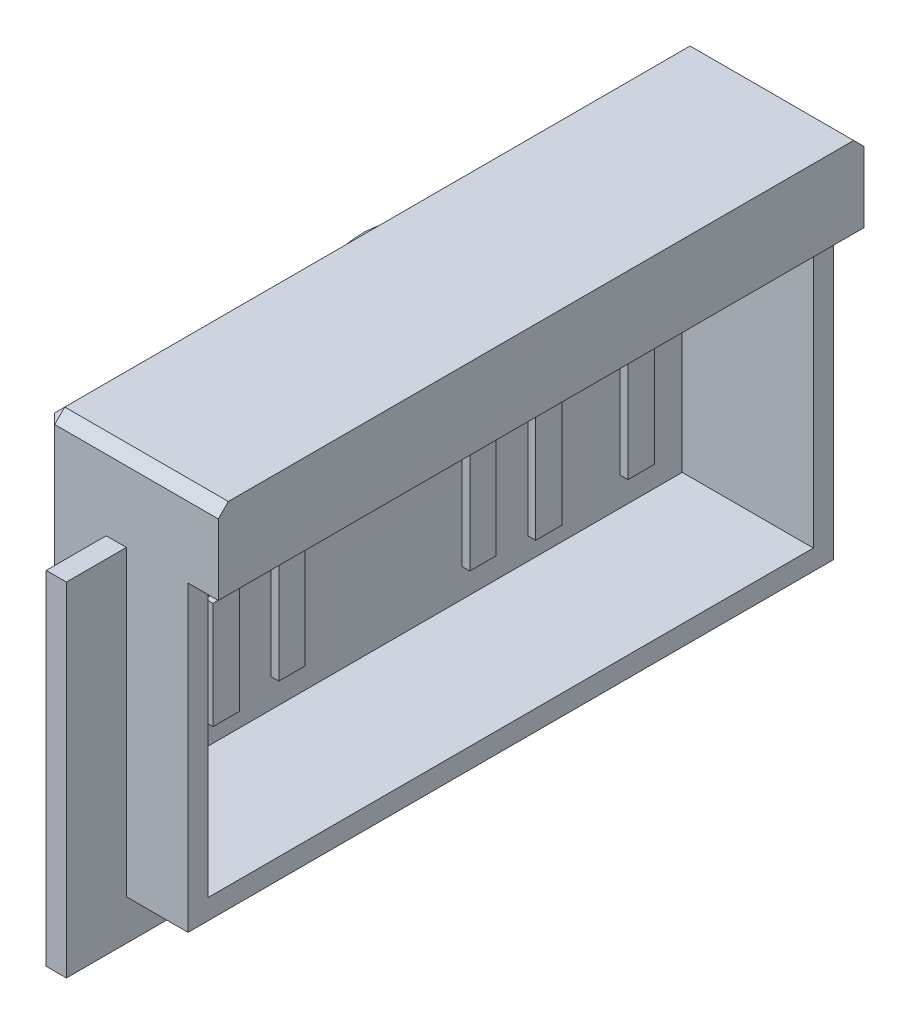
SolidWorks part; units mm, degrees
ref_plane "前视基准面" through (0, 0, 0) normal (0, 0, 1) x (1, 0, 0)
ref_plane "上视基准面" through (0, 0, 0) normal (0, 1, 0) x (1, 0, 0)
ref_plane "右视基准面" through (0, 0, 0) normal (1, 0, 0) x (0, 0, -1)
other "Configuration Table"
sketch "草图1" plane through (0, 0, 0) normal (0, 1, 0) x (1, 0, 0)
  line L0 (-2, 0) -> (0, 0)
  line L1 (0, 0) -> (0, 5.9476)
  line L2 (0, 5.9476) -> (6.111, 5.9476)
  line L3 (6.111, 5.9476) -> (6.111, 69.9476)
  line L5 (-8.111, 5.9476) -> (-8.111, 69.9476)
  line L6 (-2, 5.9476) -> (-8.111, 5.9476)
  line L7 (-2, 0) -> (-2, 5.9476)
  line L8 (-2, 75.8953) -> (-2, 69.9476)
  line L9 (-2, 69.9476) -> (-8.111, 69.9476)
  line L10 (0, 69.9476) -> (6.111, 69.9476)
  line L11 (0, 75.8953) -> (0, 69.9476)
  line L12 (-2, 75.8953) -> (0, 75.8953)
  point P14 (6.111, 37.9476)
  dimension "D2" = 5.9476
  dimension "D3" = 6.111
  dimension "D4" = 32
extrude "凸台-拉伸1" add sketch "草图1" along normal blind 38 contours L12 L8 L9 L5 L6 L7 L0 L1 L2 L3 L10 L11 region at (-1, 0, -37.9476)
sketch "草图2" plane through (6.111, 0, 0) normal (1, 0, 0) x (0, 0, -1)
  line L1 (7.9476, 2) -> (67.9476, 2)
  line L2 (7.9476, 2) -> (7.9476, 36)
  line L3 (7.9476, 36) -> (67.9476, 36)
  line L4 (67.9476, 2) -> (67.9476, 36)
  line L5 (7.9476, 2) -> (67.9476, 36) construction
  line L6 (7.9476, 36) -> (67.9476, 2) construction
  point P0 (37.9476, 19)
extrude "切除-拉伸1" cut sketch "草图2" against normal blind 13
sketch "草图3" plane through (-8.111, 0, 0) normal (-1, 0, 0) x (0, 0, 1)
  line L0 (-69.9476, 19) -> (-5.9476, 19)
  line L3 (-37.9476, 38) -> (-37.9476, 36.6686)
  line L6 (-69.9476, 38) -> (-58.2469, 31.0527)
  line L8 (-5.9476, 38) -> (-17.6484, 31.0527)
  line L9 (-69.9476, 19) -> (-58.2469, 25.9473)
  line L10 (-5.9476, 19) -> (-17.6484, 25.9473)
  line L11 (-37.9476, 0) -> (-29.779, 4.8501)
  line L12 (-37.9476, 0) -> (-52.6394, 8.7232)
  line L13 (-48.9476, 28.5) -> (-46.1054, 28.5)
  line L14 (-52.6394, 9.5) -> (-48.7219, 9.5)
  line L15 (-55.2559, 4.2066) -> (-52.6394, 4.2066)
  line L16 (-55.2559, 4.2066) -> (-55.2559, 14.7934)
  line L17 (-55.2559, 14.7934) -> (-52.6394, 14.7934)
  line L18 (-52.6394, 4.2066) -> (-52.6394, 14.7934)
  line L19 (-63.9358, 15.4305) -> (-69.9476, 19)
  line L21 (-46.1054, 28.5) -> (-46.1054, 4.8437)
  line L22 (-29.779, 28.5) -> (-29.779, 4.8501)
  line L23 (-48.7219, 4.8437) -> (-46.1054, 4.8437)
  line L24 (-46.1054, 4.8437) -> (-46.1054, 15.4305)
  line L25 (-48.7219, 4.8437) -> (-48.7219, 15.4305)
  line L26 (-48.7219, 15.4305) -> (-46.1054, 15.4305)
  line L27 (-29.779, 4.8501) -> (-27.1625, 4.8501)
  line L28 (-27.1625, 4.8501) -> (-27.1625, 15.4369)
  line L29 (-29.779, 4.8501) -> (-29.779, 15.4369)
  line L30 (-29.779, 15.4369) -> (-27.1625, 15.4369)
  line L31 (-61.7899, 4.8437) -> (-61.7899, 15.4305)
  line L32 (-61.7899, 15.4305) -> (-64.4064, 15.4305)
  line L33 (-64.4064, 4.8437) -> (-64.4064, 15.4305)
  line L34 (-61.7899, 4.8437) -> (-64.4064, 4.8437)
  line L35 (-23.2559, 14.7934) -> (-20.6394, 14.7934)
  line L36 (-23.2559, 4.2066) -> (-23.2559, 14.7934)
  line L37 (-23.2559, 4.2066) -> (-20.6394, 4.2066)
  line L38 (-20.6394, 4.2066) -> (-20.6394, 14.7934)
  line L39 (-11.4998, 4.8501) -> (-11.4998, 15.4369)
  line L40 (-11.4998, 15.4369) -> (-14.1163, 15.4369)
  line L41 (-14.1163, 4.8501) -> (-14.1163, 15.4369)
  line L42 (-11.4998, 4.8501) -> (-14.1163, 4.8501)
  line L43 (-49.6484, 25.9473) -> (-29.779, 14.1499)
  line L44 (-49.6484, 31.0527) -> (-37.9476, 38)
  line L45 (-37.9476, 20.3314) -> (-37.9476, 0)
  line L46 (-29.779, 28.5) -> (-26.9476, 28.5)
  line L47 (-26.2469, 31.0527) -> (-37.9476, 38)
  line L48 (-26.2469, 25.9473) -> (-46.1054, 14.1563)
  line L49 (-20.6394, 8.7232) -> (-5.9476, 0)
  line L50 (-20.6394, 10.2768) -> (-14.1163, 14.1499)
  line L51 (-11.9487, 15.4369) -> (-5.9476, 19)
  line L52 (-27.1625, 9.5) -> (-23.2559, 9.5)
  line L53 (-27.1625, 12.5963) -> (-23.2559, 10.2768)
  line L54 (-27.1625, 6.4037) -> (-23.2559, 8.7232)
  line L55 (-48.7219, 12.6028) -> (-52.6394, 10.2768)
  line L56 (-46.1054, 9.5) -> (-29.779, 9.5)
  line L57 (-55.2559, 10.2768) -> (-61.7899, 14.1563)
  line L58 (-55.2559, 8.7232) -> (-69.9476, 0)
  circle A0 centre (-53.9476, 28.5) radius 5
  circle A1 centre (-21.9476, 28.5) radius 5
  circle A2 centre (-37.9476, 28.5) radius 8.1686
  point P27 (-53.9476, 9.5)
  point P50 (-21.9476, 9.5)
extrude "切除-拉伸4" cut sketch "草图3" against normal blind 31 contours A2 L13 L21 | A0 | A1 | L42 L39 L40 L41 | L37 L38 L35 L36 | L30 L22 L29 L27 L28 | L26 L25 L12 L21 L24 | L15 L18 L17 L16 | L34 L31 L32 L33 | L25 L23 L12 region at (-8.111, 28.5, -53.9476) region at (-8.111, 10.1371, -63.0981) region at (-8.111, 10.5152, -47.3791) region at (-8.111, 28.5, -37.9475) region at (-8.111, 10.1435, -28.4708) region at (-8.111, 9.5, -53.9476) region at (-8.111, 28.5, -21.9476) region at (-8.111, 10.1435, -12.808) region at (-8.111, 5.3615, -47.8498) region at (-8.111, 9.5, -21.9476)
sketch "草图4" plane through (0, 0, 0) normal (0, -1, 0) x (1, 0, 0)
  line L1 (-2, 0) -> (0, 0)
  line L2 (-2, 0) -> (-2, -75.8953)
  line L3 (-2, -75.8953) -> (0, -75.8953)
  line L4 (0, 0) -> (0, -75.8953)
extrude "凸台-拉伸3" add sketch "草图4" along normal blind 4
sketch "草图5" plane through (-2, 0, 0) normal (-1, 0, 0) x (0, 0, 1)
  line L0 (-69.9476, 38) -> (-69.9476, 0) construction
  line L1 (-75.8953, 38) -> (-69.9476, 38)
  line L2 (-75.8953, 38) -> (-75.8953, 30)
  line L3 (-75.8953, 30) -> (-69.9476, 30)
  line L4 (-69.9476, 38) -> (-69.9476, 30)
  line L5 (-5.9476, 38) -> (-5.9476, 0) construction
  line L6 (0, 38) -> (-5.9476, 38)
  line L7 (0, 38) -> (0, 30)
  line L8 (0, 30) -> (-5.9476, 30)
  line L9 (-5.9476, 38) -> (-5.9476, 30)
  dimension "D1" = 8
  dimension "D2" = 8
extrude "切除-拉伸5" cut sketch "草图5" against normal blind 4
sketch "草图6" plane through (6.111, 0, 0) normal (1, 0, 0) x (0, 0, -1)
  line L1 (5.9476, 38) -> (69.9476, 38)
  line L2 (5.9476, 38) -> (5.9476, 30)
  line L3 (5.9476, 30) -> (69.9476, 30)
  line L4 (69.9476, 38) -> (69.9476, 30)
extrude "凸台-拉伸4" add sketch "草图6" along normal blind 3
sketch "草图8" plane through (-8.111, 0, 0) normal (-1, 0, 0) x (0, 0, 1)
  line L0 (-56.2426, 3.3035) -> (-51.6527, 3.3035)
  line L1 (-65.3931, 3.9406) -> (-60.8031, 3.9406)
  line L2 (-65.3931, 3.9406) -> (-65.3931, 16.3336)
  line L3 (-65.3931, 16.3336) -> (-60.8031, 16.3336)
  line L4 (-60.8031, 3.9406) -> (-60.8031, 16.3336)
  line L6 (-29.8007, 4.8373) -> (-27.1625, 4.8373)
  line L11 (-51.6527, 3.3035) -> (-51.6527, 15.6965)
  line L12 (-29.8007, 4.8373) -> (-29.8007, 15.4369)
  line L13 (-45.1187, 3.9406) -> (-45.1187, 16.3336)
  line L14 (-49.7087, 16.3336) -> (-45.1187, 16.3336)
  line L15 (-49.7087, 3.9406) -> (-49.7087, 16.3336)
  line L16 (-49.7087, 3.9406) -> (-45.1187, 3.9406)
  line L17 (-29.8007, 15.4369) -> (-27.1625, 15.4369)
  line L18 (-37.9476, 36.6686) -> (-37.9476, 20.3314)
  line L19 (-56.2426, 15.6965) -> (-51.6527, 15.6965)
  line L20 (-56.2426, 3.3035) -> (-56.2426, 15.6965)
  line L21 (-27.1625, 4.8373) -> (-27.1625, 15.4369)
  line L22 (-64.4064, 4.8437) -> (-61.7899, 4.8437)
  line L23 (-64.4064, 4.8437) -> (-64.4064, 15.4305)
  line L24 (-64.4064, 15.4305) -> (-61.7899, 15.4305)
  line L25 (-61.7899, 4.8437) -> (-61.7899, 15.4305)
  line L28 (-55.2559, 4.2066) -> (-52.6394, 4.2066)
  line L29 (-55.2559, 4.2066) -> (-55.2559, 14.7934)
  line L30 (-55.2559, 14.7934) -> (-52.6394, 14.7934)
  line L31 (-52.6394, 4.2066) -> (-52.6394, 14.7934)
  line L32 (-46.1054, 4.8437) -> (-48.7219, 4.8437)
  line L33 (-46.1054, 4.8437) -> (-46.1054, 15.4305)
  line L34 (-46.1054, 15.4305) -> (-48.7219, 15.4305)
  line L35 (-48.7219, 4.8437) -> (-48.7219, 15.4305)
  line L41 (-23.2559, 4.2066) -> (-23.2559, 14.7934)
  line L42 (-20.6394, 14.7934) -> (-23.2559, 14.7934)
  line L43 (-20.6394, 4.2066) -> (-20.6394, 14.7934)
  line L44 (-20.6394, 4.2066) -> (-23.2559, 4.2066)
  line L45 (-14.1054, 4.8437) -> (-14.1054, 15.4305)
  line L46 (-11.4889, 15.4305) -> (-14.1054, 15.4305)
  line L47 (-11.4889, 4.8437) -> (-11.4889, 15.4305)
  line L48 (-11.4889, 4.8437) -> (-14.1054, 4.8437)
  line L49 (-19.6527, 3.3035) -> (-19.6527, 15.6965)
  line L50 (-19.6527, 15.6965) -> (-24.2426, 15.6965)
  line L51 (-26.1866, 3.9406) -> (-30.7766, 3.9406)
  line L52 (-26.1866, 3.9406) -> (-26.1866, 16.3336)
  line L53 (-26.1866, 16.3336) -> (-30.7766, 16.3336)
  line L54 (-30.7766, 3.9406) -> (-30.7766, 16.3336)
  line L55 (-24.2426, 3.3035) -> (-24.2426, 15.6965)
  line L56 (-15.0922, 3.9406) -> (-15.0922, 16.3336)
  line L57 (-10.5022, 16.3336) -> (-15.0922, 16.3336)
  line L58 (-10.5022, 3.9406) -> (-10.5022, 16.3336)
  line L59 (-10.5022, 3.9406) -> (-15.0922, 3.9406)
  line L60 (-19.6527, 3.3035) -> (-24.2426, 3.3035)
  line M32 (-29.779, 15.4369) -> (-27.1625, 15.4369)
  line M33 (-27.1625, 15.4369) -> (-27.1625, 4.8501)
  line M47 (-11.4998, 4.8501) -> (-14.1163, 4.8501)
  line M48 (-14.1163, 4.8501) -> (-14.1163, 15.4369)
  line M49 (-14.1163, 15.4369) -> (-11.4998, 15.4369)
  line M50 (-11.4998, 15.4369) -> (-11.4998, 4.8501)
extrude "凸台-拉伸12" add sketch "草图8" along normal blind 0.5 separate body contours L1 L4 L3 L2 | L20 L0 L11 L19 | L15 L16 L13 L14 | L54 L51 L52 L53 L21 L6 L12 L17 M32 M33 | L60 L49 L50 L55 | L59 L58 L57 L56 L47 L48 L45 L46 M47 M48 M49 M50 region at (-8.111, 9.5, -56.1105) region at (-8.111, 10.1371, -65.2609) region at (-8.111, 4.0727, -47.4137) region at (-8.111, 3.4356, -21.9476) region at (-8.111, 4.0727, -28.4816) region at (-8.111, 10.1371, -14.96)
sketch "草图7" plane through (-8.111, 0, 0) normal (-1, 0, 0) x (0, 0, 1)
  line L0 (-55.2559, 4.2066) -> (-52.6394, 4.2066) construction
  line L1 (-64.4064, 15.4305) -> (-61.7899, 15.4305)
  line L2 (-64.4064, 15.4305) -> (-64.4064, 4.8437)
  line L3 (-64.4064, 4.8437) -> (-61.7899, 4.8437)
  line L4 (-61.7899, 15.4305) -> (-61.7899, 4.8437)
  line L5 (-55.2559, 14.7934) -> (-52.6394, 14.7934)
  line L6 (-55.2559, 14.7934) -> (-55.2559, 4.2066)
  line L7 (-55.2559, 4.2066) -> (-52.6394, 4.2066)
  line L8 (-52.6394, 14.7934) -> (-52.6394, 4.2066)
  line L9 (-52.6394, 4.2066) -> (-52.6394, 14.7934) construction
  line L10 (-37.9476, 36.6686) -> (-37.9476, 20.3314)
  line L11 (-48.7219, 15.4305) -> (-46.1054, 15.4305)
  line L12 (-48.7219, 15.4305) -> (-48.7219, 4.8437)
  line L13 (-48.7219, 4.8437) -> (-46.1054, 4.8437)
  line L14 (-46.1054, 15.4305) -> (-46.1054, 4.8437)
  line L15 (-27.1734, 4.8437) -> (-29.7899, 4.8437)
  line L16 (-29.7899, 15.4305) -> (-29.7899, 4.8437)
  line L17 (-27.1734, 15.4305) -> (-29.7899, 15.4305)
  line L18 (-27.1734, 15.4305) -> (-27.1734, 4.8437)
  line L19 (-20.6394, 4.2066) -> (-23.2559, 4.2066)
  line L20 (-23.2559, 14.7934) -> (-23.2559, 4.2066)
  line L21 (-20.6394, 14.7934) -> (-23.2559, 14.7934)
  line L22 (-20.6394, 14.7934) -> (-20.6394, 4.2066)
  line L23 (-11.4889, 4.8437) -> (-14.1054, 4.8437)
  line L24 (-14.1054, 15.4305) -> (-14.1054, 4.8437)
  line L25 (-11.4889, 15.4305) -> (-14.1054, 15.4305)
  line L26 (-11.4889, 15.4305) -> (-11.4889, 4.8437)
  arc A0 (-34.7109, 36) -> (-41.1844, 36) centre (-37.9476, 28.5) ccw construction
  arc A1 (-46.1054, 28.0794) -> (-46.1163, 28.5) centre (-37.9476, 28.5) ccw construction
  line M16 (-20.6394, 4.2066) -> (-23.2559, 4.2066)
  line M17 (-23.2559, 4.2066) -> (-23.2559, 14.7934)
  line M18 (-23.2559, 14.7934) -> (-20.6394, 14.7934)
  line M19 (-20.6394, 14.7934) -> (-20.6394, 4.2066)
  line M20 (-52.6394, 4.2066) -> (-55.2559, 4.2066)
  line M21 (-55.2559, 4.2066) -> (-55.2559, 14.7934)
  line M22 (-55.2559, 14.7934) -> (-52.6394, 14.7934)
  line M23 (-52.6394, 14.7934) -> (-52.6394, 4.2066)
  line M31 (-29.779, 4.8501) -> (-29.779, 15.4369)
  line M34 (-27.1625, 4.8501) -> (-29.779, 4.8501)
  line M35 (-61.7899, 15.4305) -> (-61.7899, 4.8437)
  line M36 (-61.7899, 4.8437) -> (-64.4064, 4.8437)
  line M37 (-64.4064, 4.8437) -> (-64.4064, 15.4305)
  line M38 (-64.4064, 15.4305) -> (-61.7899, 15.4305)
  line M39 (-48.7219, 4.8437) -> (-48.7219, 15.4305)
  line M40 (-48.7219, 15.4305) -> (-46.1054, 15.4305)
  line M41 (-46.1054, 15.4305) -> (-46.1054, 4.8437)
  line M42 (-46.1054, 4.8437) -> (-48.7219, 4.8437)
  line M43 (-11.4998, 15.4369) -> (-11.4998, 4.8501)
  line M44 (-11.4998, 4.8501) -> (-14.1163, 4.8501)
extrude "凸台-拉伸5" add sketch "草图7" along normal blind 1.5 and the other way blind 2 separate body contours M35 M38 M37 M36 | M20 M23 M22 M21 | M39 M42 M41 M40 | L18 L17 M31 M34 | M16 M19 M18 M17 | L25 L24 M43 M44 region at (-8.111, 10.1371, -63.0981) region at (-8.111, 9.5, -53.9476) region at (-8.111, 10.1371, -47.4137) region at (-8.111, 10.1403, -28.4762) region at (-8.111, 9.5, -21.9476) region at (-8.111, 10.1403, -12.8026)
sketch "草图9" plane through (-8.111, 0, 0) normal (-1, 0, 0) x (0, 0, 1)
  circle A0 centre (-53.9476, 28.5) radius 5
  circle A1 centre (-21.9476, 28.5) radius 5
extrude "凸台-拉伸13" add sketch "草图9" along normal blind 0.5 separate body
sketch "草图10" plane through (-8.111, 0, 0) normal (-1, 0, 0) x (0, 0, 1)
  circle A0 centre (-37.9476, 28.5) radius 8.1686
extrude "凸台-拉伸16" add sketch "草图10" along normal blind 0.5 separate body
sketch "草图11" plane through (-8.611, 0, 0) normal (-1, 0, 0) x (0, 0, 1)
  circle A0 centre (-37.9476, 28.5) radius 3.5195
extrude "凸台-拉伸17" add sketch "草图11" along normal blind 1
sketch "草图12" plane through (-8.611, 0, 0) normal (-1, 0, 0) x (0, 0, 1)
  circle A0 centre (-37.9476, 28.5) radius 4.1659
  circle A1 centre (-37.9476, 28.5) radius 3.5195
extrude "凸台-拉伸18" add sketch "草图12" along normal blind 2
sketch "草图13" plane through (-9.611, 0, 0) normal (-1, 0, 0) x (0, 0, 1)
  circle A0 centre (-37.9476, 28.5) radius 1.9999
extrude "切除-拉伸6" cut sketch "草图13" against normal blind 2
chamfer "倒角1" distance 1 angle 45 6 edges at (-8.111, 19, -69.9476) (-8.111, 38, -37.9476) (-8.111, 19, -5.9476) (-8.111, 0, -37.9476) (0.5, 38, -5.9476) (0.5, 38, -69.9476)
